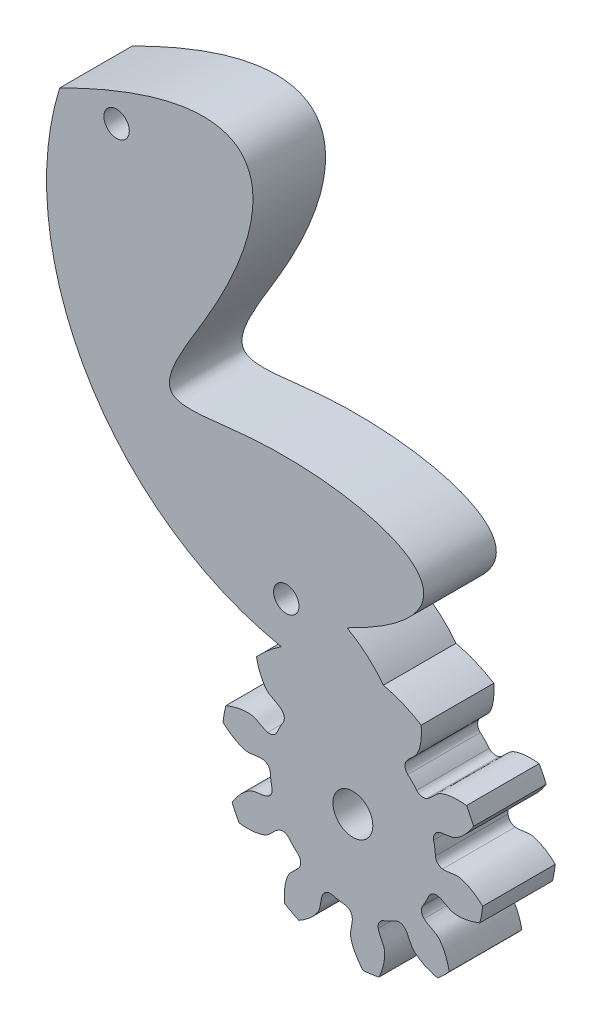
SolidWorks part; units mm, degrees
material "3003 Alaşım"
ref_plane "前视基准面" through (0, 0, 0) normal (0, 0, 1) x (1, 0, 0)
ref_plane "上视基准面" through (0, 0, 0) normal (0, 1, 0) x (1, 0, 0)
ref_plane "右视基准面" through (0, 0, 0) normal (1, 0, 0) x (0, 0, -1)
sketch "草图1" plane through (0, 0, 0) normal (0, 0, 1) x (1, 0, 0)
  line L0 (-50, 0) -> (-25, 0) construction
  line L1 (-28.7348, 74.7114) -> (-28.7348, -58.328) construction
  line L31 (-28.7348, -54.9949) -> (-28.7348, -58.328)
  line L34 (-28.7348, -66.107) -> (-16.1671, -66.107) construction
  arc A16 (-32.5692, -50.9983) -> (-62.8387, 0.35) centre (-24.3784, -11.5738) cw
  arc A17 (-23.252, -44.2645) -> (-15.0404, -59.3926) centre (-31.0005, -58.2631) cw
  arc A18 (-28.7348, -58.328) -> (-15.0404, -59.3926) centre (-22.4509, -66.107) ccw
  arc A20 (-32.5692, -50.9983) -> (-28.7348, -54.9949) centre (-32.7348, -54.9949) cw
  circle A22 centre (-22.4509, -66.107) radius 5
  circle A26 centre (-31.6201, -45.0019) radius 1.75
  circle A27 centre (-55, 0) radius 1.75
  spline S0 degree 3 poles (-62.8387, 0.35) (-32.3892, 15.6125) (-31.8503, -2.5111) (-51.8071, -30.7499) (-24.5472, -25.1943) (-0.1216, -33.0016) (-23.252, -44.2645) knots 0 0 0 0 0.423155 0.543124 0.634591 1 1 1 1
  point P9 (-25, 0)
  point P10 (0, 0)
  point P64 (-28.7348, -52.6717)
  point P69 (-2.507, 0.35)
  dimension "D4" = 3.5
  dimension "D6" = 16
  dimension "D7" = 4
  dimension "D9" = 10
  dimension "D10" = 3.5
  dimension "D3" = 25
extrude "凸台拉伸1" add sketch "草图1" along normal blind 1
extrude "凸台-拉伸1" add sketch "草图1<2>" along normal blind 10
sketch "草图1<2>" plane through (0, 0, 0) normal (0, 0, 1) x (1, 0, 0) same geometry as "草图1"
sketch "草图7" plane through (0, 0, 0) normal (0, 0, 1) x (1, 0, 0)
  line L0 (-22.4509, -66.107) -> (-22.4509, -48.107) construction
  arc A0 (-32.0748, -59.9963) -> (-32.8986, -61.5456) centre (-22.4509, -66.107) ccw
  arc A1 (-35.9543, -51.7661) -> (-41.8911, -62.9316) centre (-22.4509, -66.107) ccw
  arc A2 (-32.8986, -61.5456) -> (-34.1894, -62.2026) centre (-33.9434, -61.0895) cw
  arc A3 (-32.2519, -58.5588) -> (-32.0748, -59.9963) centre (-33.0372, -59.3852) cw
  circle A4 centre (-22.4509, -66.107) radius 14.5222 construction
  circle A5 centre (-22.4509, -66.107) radius 18 construction
  circle A6 centre (-22.4509, -66.107) radius 11.4 construction
  circle A7 centre (-22.4509, -66.107) radius 15 construction
  spline S0 degree 3 poles (-32.2519, -58.5588) (-32.7705, -58.066) (-33.6057, -57.8737) (-34.2019, -57.3264) (-34.2828, -57.24) (-34.3453, -57.1694) (-34.4147, -57.0856) (-34.4903, -56.9882) (-34.5713, -56.8768) (-34.657, -56.7509) (-34.7464, -56.6101) (-34.8387, -56.4541) (-34.9331, -56.2825) (-35.0285, -56.0951) (-35.1242, -55.8917) (-35.2192, -55.6721) (-35.3125, -55.436) (-35.4032, -55.1835) (-35.4903, -54.9145) (-35.573, -54.6289) (-35.6502, -54.3268) (-35.721, -54.0082) (-35.7843, -53.6733) (-35.8393, -53.3223) (-35.885, -52.9553) (-35.9331, -52.4354) (-35.9506, -52.0368) (-35.9543, -51.7661) knots 0.111786 0.111786 0.111786 0.111786 0.344236 0.363717 0.372294 0.382431 0.394128 0.407384 0.422199 0.438574 0.456508 0.476002 0.497056 0.519669 0.543841 0.569573 0.596865 0.625716 0.656126 0.688097 0.721626 0.756715 0.793364 0.831572 0.87134 0.912667 1 1 1 1
  spline S1 degree 3 poles (-34.1894, -62.2026) (-34.8879, -62.0482) (-35.5143, -61.4634) (-36.3015, -61.2751) (-36.4184, -61.2564) (-36.5119, -61.2441) (-36.6201, -61.2334) (-36.7431, -61.2252) (-36.8808, -61.2203) (-37.0331, -61.2197) (-37.1998, -61.2243) (-37.3808, -61.235) (-37.5758, -61.2527) (-37.7845, -61.2783) (-38.0066, -61.3128) (-38.2418, -61.3569) (-38.4897, -61.4115) (-38.7498, -61.4775) (-39.0215, -61.5557) (-39.3045, -61.6469) (-39.5982, -61.7518) (-39.9018, -61.8713) (-40.2149, -62.006) (-40.5367, -62.1567) (-40.8665, -62.3241) (-41.3244, -62.5749) (-41.6646, -62.7833) (-41.8911, -62.9316) knots 0.111786 0.111786 0.111786 0.111786 0.344236 0.363717 0.372294 0.382431 0.394128 0.407384 0.422199 0.438574 0.456508 0.476002 0.497056 0.519669 0.543841 0.569573 0.596865 0.625716 0.656126 0.688097 0.721626 0.756715 0.793364 0.831572 0.87134 0.912667 1 1 1 1
  dimension "D1" = 1.14
  dimension "Db" = 29.0444
  dimension "Da" = 36
  dimension "Df" = 22.8
  dimension "Dn" = 30
sketch "草图8" plane through (0, 0, 10) normal (0, 0, 1) x (1, 0, 0)
  circle A0 centre (-22.4509, -66.107) radius 18
extrude "凸台-拉伸3" add sketch "草图8" against normal blind 10
sketch "草图9" plane through (0, 0, 10) normal (0, 0, 1) x (1, 0, 0)
  circle A0 centre (-22.4509, -66.107) radius 2.75
  dimension "D1" = 5.5
extrude "切除-拉伸3" cut sketch "草图7" along normal blind 10
extrude "切除-拉伸4" cut sketch "草图9" against normal blind 10
pattern_circular "阵列(圆周)3" count 8 every 36 about axis through (-22.4509, -66.107, 0) along (0, 0, 1) of "切除-拉伸3"
